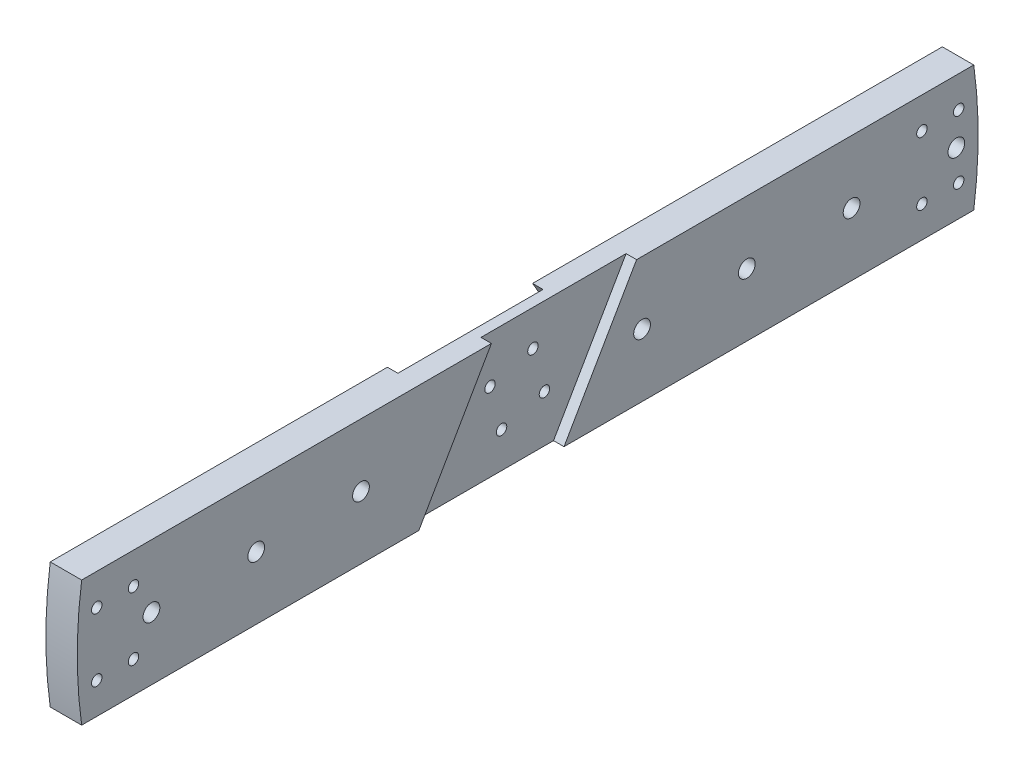
SolidWorks part; units mm, degrees
note: The reader was unsure of these and kept them because the rebuilt part matched: shared geometry of "Sketch3<5>".
ref_plane "Front Plane" through (0, 0, 0) normal (0, 0, 1) x (1, 0, 0)
ref_plane "Top Plane" through (0, 0, 0) normal (0, 1, 0) x (1, 0, 0)
ref_plane "Right Plane" through (0, 0, 0) normal (1, 0, 0) x (0, 0, -1)
sketch "Sketch1" plane through (0, 0, 0) normal (1, 0, 0) x (0, 0, -1)
  circle A0 centre (0, 0) radius 273.05
  point P0 (0, 0)
  dimension "D1" = 546.1
curve "Helix/Spiral1"
sketch "Sketch2" plane through (0, 0, 0) normal (1, 0, 0) x (0, 0, -1)
  line L0 (-273.05, 0) -> (273.05, 0) construction
  line L1 (-270.3788, -38.1) -> (270.3788, -38.1)
  line L3 (-270.3788, 38.1) -> (270.3788, 38.1)
  line L4 (270.3788, -38.1) -> (270.3788, 38.1) construction
  line L5 (-270.3788, -38.1) -> (270.3788, 38.1) construction
  line L6 (-270.3788, 38.1) -> (270.3788, -38.1) construction
  line L7 (273.05, 0) -> (228.6, 0) construction
  line L8 (38.1, -38.1) -> (-38.1, -38.1)
  line L9 (38.1, -38.1) -> (38.1, 38.1)
  line L10 (38.1, 38.1) -> (-38.1, 38.1)
  line L11 (-38.1, -38.1) -> (-38.1, 38.1)
  line L12 (38.1, -38.1) -> (-38.1, 38.1) construction
  line L13 (38.1, 38.1) -> (-38.1, -38.1) construction
  line L14 (226.3636, 31.8977) -> (270.3788, 38.1)
  line L15 (16.4978, -9.525) -> (-9.525, -16.4978)
  line L16 (273.05, 0) -> (250.825, 0)
  line L17 (250.825, 0) -> (228.6, 0)
  line L18 (16.4978, -9.525) -> (9.525, 16.4978)
  line L19 (-9.525, -16.4978) -> (-16.4978, 9.525)
  line L20 (0, 38.1) -> (0, -38.1) construction
  line L21 (9.525, 16.4978) -> (-16.4978, 9.525)
  line L26 (0, 0) -> (21.997, 38.1)
  circle A0 centre (0, 0) radius 273.05 construction
  circle A3 centre (196.3202, 0) radius 5.08
  circle A4 centre (132.8204, 0) radius 5.08
  circle A6 centre (-101.0705, 0) radius 5.08
  circle A7 centre (-164.5703, 0) radius 5.08
  circle A8 centre (-228.0701, 0) radius 5.08
  circle A9 centre (0, 0) radius 273.05
  circle A10 centre (0, 0) radius 228.6
  arc A11 (247.9144, -38.1) -> (250.825, 0) centre (0, 0) ccw
  arc A12 (236.6653, -38.1) -> (239.7125, 0) centre (0, 0) ccw
  arc A13 (259.1518, -38.1) -> (261.9375, 0) centre (0, 0) ccw
  circle A14 centre (238.9495, -19.1108) radius 3.175
  circle A15 centre (261.2401, -19.1009) radius 3.175
  circle A16 centre (238.9495, 19.1108) radius 3.175
  circle A17 centre (261.2401, 19.1009) radius 3.175
  circle A34 centre (-16.4978, 9.525) radius 3.175
  circle A35 centre (9.525, 16.4978) radius 3.175
  circle A36 centre (-9.525, -16.4978) radius 3.175
  circle A37 centre (16.4978, -9.525) radius 3.175
  circle A38 centre (-261.2401, -19.1009) radius 3.175
  circle A39 centre (-238.9495, -19.1108) radius 3.175
  circle A40 centre (-238.9495, 19.1108) radius 3.175
  circle A41 centre (-261.2401, 19.1009) radius 3.175
  circle A42 centre (259.8208, 0) radius 5.08
  circle A43 centre (69.3206, 0) radius 5.08
  spline S0 degree 3 poles (793.7729, 2436.9325) (-868.0473, 115.5273) (-235.8062, -393.7047) (104.0483, -251.1749) (112.0797, -247.3314) (127.6988, -238.8914) (135.2864, -234.2949) (149.9478, -224.399) (157.0216, -219.0994) (170.591, -207.8536) (177.0865, -201.9073) (189.4408, -189.4299) (195.2996, -182.8989) (206.3286, -169.3195) (211.4988, -162.2712) (221.1058, -147.7289) (225.5427, -140.2351) (233.6456, -124.8774) (237.3117, -117.0137) (243.8435, -100.9949) (246.7093, -92.8399) (251.6186, -76.3196) (253.6623, -67.9542) (256.914, -51.0955) (258.1221, -42.6021) (259.6972, -25.5701) (260.0643, -17.0316) (259.9603, 0.0078) (259.4892, 8.5087) (257.7198, 25.391) (256.4215, 33.7725) (253.0164, 50.336) (250.9097, 58.5181) (245.9143, 74.6055) (243.0257, 82.5107) (236.5004, 97.9701) (232.8637, 105.5243) (220.8931, 127.5551) (211.4954, 141.3972) (190.2687, 166.8872) (178.4403, 178.5347) (152.8439, 199.2225) (139.0766, 208.2626) (110.1609, 223.4294) (95.0134, 229.556) (63.9404, 238.7068) (48.0158, 241.7309) (16.0122, 244.61) (-0.066, 244.4649) (-31.7571, 241.062) (-47.3693, 237.8044) (-77.5368, 228.3514) (-92.0913, 222.1565) (-119.6019, 207.1148) (-132.5574, 198.2684) (-156.3988, 178.3067) (-167.2843, 167.192) (-186.602, 143.1579) (-195.0339, 130.2393) (-209.1618, 103.1232) (-214.8575, 88.9267) (-223.3403, 59.8215) (-226.1274, 44.9136) (-228.7351, 14.9702) (-228.556, -0.0645) (-225.289, -29.6821) (-222.2014, -44.2642) (-213.2863, -72.4244) (-207.4591, -86.0018) (-193.3365, -111.6487) (-185.0414, -123.7176) (-166.3447, -145.9104) (-155.9437, -156.0339) (-133.472, -173.9815) (-121.4019, -181.8053) (-96.0856, -194.8941) (-82.8399, -200.159) (-55.7025, -207.9738) (-41.8113, -210.5238) (-13.9282, -212.8603) (0.063, -212.647) (27.607, -209.5159) (41.159, -206.5984) (67.312, -198.2211) (79.9123, -192.7617) (103.6955, -179.5582) (114.8778, -171.8144) (135.422, -154.3828) (144.7835, -144.6954) (161.361, -123.7861) (168.5766, -112.5646) (180.6265, -89.0479) (185.4604, -76.7532) (192.6073, -51.5835) (194.9202, -38.7091) (196.9855, -12.8863) (196.738, 0.0615) (193.7429, 25.5319) (190.9954, 38.0539) (183.156, 62.1997) (178.0643, 73.8229) (165.7798, 95.7423) (158.5874, 106.038) (142.4208, 124.9336) (133.4471, 133.5331) (114.1001, 148.7404) (103.7273, 155.348) (82.0102, 166.3588) (70.6665, 170.7619) (47.4645, 177.2408) (35.6069, 179.3167) (11.8443, 181.1107) (-0.0601, 180.8291) (-23.4569, 177.9698) (-34.9488, 175.3924) (-57.0873, 168.0908) (-67.7334, 163.3669) (-87.7891, 152.0015) (-97.1983, 145.3604) (-114.4453, 130.4588) (-122.2827, 122.1989) (-136.1199, 104.4142) (-142.1193, 94.89) (-152.0911, 74.9725) (-156.0634, 64.5798) (-161.8743, 43.3455) (-163.7131, 32.5046) (-165.2359, 10.8023) (-164.9201, -0.0586) (-162.1968, -21.3818) (-159.7894, -31.8436) (-153.0257, -51.9749) (-148.6695, -61.6439) (-138.2232, -79.8359) (-132.1334, -88.3585) (-118.4968, -103.9569) (-110.9506, -111.0324) (-94.7282, -123.4994) (-86.0527, -128.8907) (-67.9348, -137.8235) (-58.493, -141.3648) (-39.2266, -146.5079) (-29.4024, -148.1095) (-9.7603, -149.3611) (0.0571, -149.0111) (19.3067, -146.4237) (28.7385, -144.1864) (46.8626, -137.9605) (55.5545, -133.9721) (71.8827, -124.4449) (79.5187, -118.9064) (93.4685, -106.5349) (99.782, -99.7023) (110.8788, -85.0423) (115.6621, -77.2154) (123.5558, -60.8971) (126.6663, -52.4063) (131.1414, -35.1076) (132.506, -26.3002) (133.4863, -8.7184) (133.1022, 0.0556) (130.6506, 17.2317) (128.5834, 25.6333) (122.8954, 41.7502) (119.2747, 49.465) (110.6666, 63.9295) (105.6794, 70.6789) (94.5729, 82.9801) (88.454, 88.5316) (75.3564, 98.2583) (68.3781, 102.4334) (53.8594, 109.2882) (46.3196, 111.9678) (30.9886, 115.7749) (23.198, 116.9024) (7.6764, 117.6115) (-0.0541, 117.1932) (-15.1566, 114.8776) (-22.5282, 112.9804) (-36.6378, 107.8302) (-43.3755, 104.5773) (-55.9763, 96.8883) (-61.8391, 92.4524) (-72.4917, 82.6109) (-77.2812, 77.2057) (-85.6378, 65.6704) (-89.2048, 59.5407) (-95.0205, 46.8218) (-97.2692, 40.2329) (-100.4084, 26.8696) (-101.2988, 20.0957) (-101.7367, 6.6344) (-101.2842, -0.0526) (-99.1045, -13.0815) (-97.3775, -19.4231) (-92.765, -31.5255) (-89.8799, -37.2861) (-83.11, -48.0231) (-79.2254, -52.9994) (-70.649, -62.0033) (-65.9574, -66.0308) (-55.9845, -73.0173) (-50.7034, -75.9761) (-39.7841, -80.7528) (-34.1461, -82.5707) (-22.7507, -85.0419) (-16.9935, -85.6952) (-5.5924, -85.8619) (0.0512, -85.3753) (11.0065, -83.3315) (16.3179, -81.7745) (26.4131, -77.6999) (31.1966, -75.1825) (40.0699, -69.3317) (44.1596, -65.9984) (51.5149, -58.687) (54.7804, -54.7091) (60.3967, -46.2985) (62.7475, -41.8661) (66.4852, -32.7464) (67.8722, -28.0594) (69.6754, -18.6317) (70.0917, -13.8913) (69.9871, -4.5505) (69.4663, 0.0497) (67.5584, 8.9314) (66.1715, 13.2128) (62.6347, 21.3007) (60.4851, 25.1071) (55.5534, 32.1167) (52.7714, 35.3198) (46.725, 41.0265) (43.4608, 43.53) (36.6126, 47.7762) (33.0288, 49.5188) (25.7087, 52.2175) (21.9727, 53.1736) (14.5127, 54.3089) (10.789, 54.4881) (3.5085, 54.1123) (-0.0482, 53.5574) (-6.8563, 51.7854) (-10.1076, 50.5685) (-16.1884, 47.5696) (-19.0177, 45.7877) (-24.1635, 41.7751) (-26.48, 39.5444) (-30.5381, 34.763) (-32.2797, 32.2125) (-35.1557, 26.9267) (-36.2902, 24.1915) (-37.9498, 18.671) (-38.4751, 15.8859) (-38.9424, 10.3937) (-38.8845, 7.6868) (-38.2375, 2.4665) (-37.6484, -0.0467) (-36.0123, -4.7813) (-34.9655, -7.0025) (-32.5044, -11.076) (-31.0903, -12.9282) (-27.9967, -16.2103) (-26.3174, -17.6402) (-22.8011, -20.0497) (-20.9643, -21.0293) (-17.2407, -22.5352) (-15.3542, -23.0615) (-11.6333, -23.6822) (-9.7992, -23.7765) (-6.2748, -23.5759) (-4.5846, -23.281) (-1.4245, -22.3627) (0.0452, -21.7394) (56.9085, 10.3181) (-130.2763, 262.2935) (-1920.1654, -2304.1586) knots -0.153771 -0.153771 -0.153771 -0.153771 0.003906 0.003906 0.007813 0.007813 0.011719 0.011719 0.015625 0.015625 0.019531 0.019531 0.023438 0.023438 0.027344 0.027344 0.03125 0.03125 0.035156 0.035156 0.039063 0.039063 0.042969 0.042969 0.046875 0.046875 0.050781 0.050781 0.054688 0.054688 0.058594 0.058594 0.0625 0.0625 0.066406 0.066406 0.070313 0.070313 0.078125 0.078125 0.085938 0.085938 0.09375 0.09375 0.101562 0.101562 0.109375 0.109375 0.117187 0.117187 0.125 0.125 0.132812 0.132812 0.140625 0.140625 0.148437 0.148437 0.15625 0.15625 0.164062 0.164062 0.171875 0.171875 0.179687 0.179687 0.1875 0.1875 0.195312 0.195312 0.203125 0.203125 0.210937 0.210937 0.21875 0.21875 0.226562 0.226562 0.234375 0.234375 0.242187 0.242187 0.25 0.25 0.257812 0.257812 0.265625 0.265625 0.273437 0.273437 0.28125 0.28125 0.289062 0.289062 0.296875 0.296875 0.304687 0.304687 0.3125 0.3125 0.320312 0.320312 0.328125 0.328125 0.335937 0.335937 0.34375 0.34375 0.351562 0.351562 0.359375 0.359375 0.367187 0.367187 0.375 0.375 0.382812 0.382812 0.390625 0.390625 0.398437 0.398437 0.40625 0.40625 0.414062 0.414062 0.421875 0.421875 0.429687 0.429687 0.4375 0.4375 0.445312 0.445312 0.453125 0.453125 0.460937 0.460937 0.46875 0.46875 0.476562 0.476562 0.484375 0.484375 0.492187 0.492187 0.5 0.5 0.507812 0.507812 0.515625 0.515625 0.523437 0.523437 0.53125 0.53125 0.539062 0.539062 0.546875 0.546875 0.554687 0.554687 0.5625 0.5625 0.570312 0.570312 0.578125 0.578125 0.585937 0.585937 0.59375 0.59375 0.601562 0.601562 0.609375 0.609375 0.617187 0.617187 0.625 0.625 0.632812 0.632812 0.640625 0.640625 0.648438 0.648438 0.65625 0.65625 0.664062 0.664062 0.671875 0.671875 0.679688 0.679688 0.6875 0.6875 0.695312 0.695312 0.703125 0.703125 0.710938 0.710938 0.71875 0.71875 0.726562 0.726562 0.734375 0.734375 0.742188 0.742188 0.75 0.75 0.757812 0.757812 0.765625 0.765625 0.773438 0.773438 0.78125 0.78125 0.789062 0.789062 0.796875 0.796875 0.804688 0.804688 0.8125 0.8125 0.820312 0.820312 0.828125 0.828125 0.835938 0.835938 0.84375 0.84375 0.851562 0.851562 0.859375 0.859375 0.867188 0.867188 0.875 0.875 0.882813 0.882813 0.890625 0.890625 0.898438 0.898438 0.90625 0.90625 0.914063 0.914063 0.921875 0.921875 0.929688 0.929688 0.9375 0.9375 0.945313 0.945313 0.953125 0.953125 0.960938 0.960938 0.96875 0.96875 0.976563 0.976563 0.984375 0.984375 0.992188 0.992188 1.318271 1.318271 1.318271 1.318271 only from (70.6705, -263.746) to (4.9305, -18.4009) construction
  spline S1 degree 3 poles (70.6705, -263.746) (79.216, -261.1139) (87.6164, -258.0662) (104.0483, -251.1749) (112.0797, -247.3314) (127.6988, -238.8914) (135.2864, -234.2949) (149.9478, -224.399) (157.0216, -219.0994) (170.591, -207.8536) (177.0865, -201.9073) (189.4408, -189.4299) (195.2996, -182.8989) (206.3286, -169.3195) (211.4988, -162.2712) (221.1058, -147.7289) (225.5427, -140.2351) (233.6456, -124.8774) (237.3117, -117.0137) (243.8435, -100.9949) (246.7093, -92.8399) (251.6186, -76.3196) (253.6623, -67.9542) (256.914, -51.0955) (258.1221, -42.6021) (259.6972, -25.5701) (260.0643, -17.0316) (259.9603, 0.0078) (259.4892, 8.5087) (257.7198, 25.391) (256.4215, 33.7725) (253.0164, 50.336) (250.9097, 58.5181) (245.9143, 74.6055) (243.0257, 82.5107) (236.5004, 97.9701) (232.8637, 105.5243) (220.8931, 127.5551) (211.4954, 141.3972) (190.2687, 166.8872) (178.4403, 178.5347) (152.8439, 199.2225) (139.0766, 208.2626) (110.1609, 223.4294) (95.0134, 229.556) (63.9404, 238.7068) (48.0158, 241.7309) (16.0122, 244.61) (-0.066, 244.4649) (-31.7571, 241.062) (-47.3693, 237.8044) (-77.5368, 228.3514) (-92.0913, 222.1565) (-119.6019, 207.1148) (-132.5574, 198.2684) (-156.3988, 178.3067) (-167.2843, 167.192) (-186.602, 143.1579) (-195.0339, 130.2393) (-209.1618, 103.1232) (-214.8575, 88.9267) (-223.3403, 59.8215) (-226.1274, 44.9136) (-228.7351, 14.9702) (-228.556, -0.0645) (-225.289, -29.6821) (-222.2014, -44.2642) (-213.2863, -72.4244) (-207.4591, -86.0018) (-193.3365, -111.6487) (-185.0414, -123.7176) (-166.3447, -145.9104) (-155.9437, -156.0339) (-133.472, -173.9815) (-121.4019, -181.8053) (-96.0856, -194.8941) (-82.8399, -200.159) (-55.7025, -207.9738) (-41.8113, -210.5238) (-13.9282, -212.8603) (0.063, -212.647) (27.607, -209.5159) (41.159, -206.5984) (67.312, -198.2211) (79.9123, -192.7617) (103.6955, -179.5582) (114.8778, -171.8144) (135.422, -154.3828) (144.7835, -144.6954) (161.361, -123.7861) (168.5766, -112.5646) (180.6265, -89.0479) (185.4604, -76.7532) (192.6073, -51.5835) (194.9202, -38.7091) (196.9855, -12.8863) (196.738, 0.0615) (193.7429, 25.5319) (190.9954, 38.0539) (183.156, 62.1997) (178.0643, 73.8229) (165.7798, 95.7423) (158.5874, 106.038) (142.4208, 124.9336) (133.4471, 133.5331) (114.1001, 148.7404) (103.7273, 155.348) (82.0102, 166.3588) (70.6665, 170.7619) (47.4645, 177.2408) (35.6069, 179.3167) (11.8443, 181.1107) (-0.0601, 180.8291) (-23.4569, 177.9698) (-34.9488, 175.3924) (-57.0873, 168.0908) (-67.7334, 163.3669) (-87.7891, 152.0015) (-97.1983, 145.3604) (-114.4453, 130.4588) (-122.2827, 122.1989) (-136.1199, 104.4142) (-142.1193, 94.89) (-152.0911, 74.9725) (-156.0634, 64.5798) (-161.8743, 43.3455) (-163.7131, 32.5046) (-165.2359, 10.8023) (-164.9201, -0.0586) (-162.1968, -21.3818) (-159.7894, -31.8436) (-153.0257, -51.9749) (-148.6695, -61.6439) (-138.2232, -79.8359) (-132.1334, -88.3585) (-118.4968, -103.9569) (-110.9506, -111.0324) (-94.7282, -123.4994) (-86.0527, -128.8907) (-67.9348, -137.8235) (-58.493, -141.3648) (-39.2266, -146.5079) (-29.4024, -148.1095) (-9.7603, -149.3611) (0.0571, -149.0111) (19.3067, -146.4237) (28.7385, -144.1864) (46.8626, -137.9605) (55.5545, -133.9721) (71.8827, -124.4449) (79.5187, -118.9064) (93.4685, -106.5349) (99.782, -99.7023) (110.8788, -85.0423) (115.6621, -77.2154) (123.5558, -60.8971) (126.6663, -52.4063) (131.1414, -35.1076) (132.506, -26.3002) (133.4863, -8.7184) (133.1022, 0.0556) (130.6506, 17.2317) (128.5834, 25.6333) (122.8954, 41.7502) (119.2747, 49.465) (110.6666, 63.9295) (105.6794, 70.6789) (94.5729, 82.9801) (88.454, 88.5316) (75.3564, 98.2583) (68.3781, 102.4334) (53.8594, 109.2882) (46.3196, 111.9678) (30.9886, 115.7749) (23.198, 116.9024) (7.6764, 117.6115) (-0.0541, 117.1932) (-15.1566, 114.8776) (-22.5282, 112.9804) (-36.6378, 107.8302) (-43.3755, 104.5773) (-55.9763, 96.8883) (-61.8391, 92.4524) (-72.4917, 82.6109) (-77.2812, 77.2057) (-85.6378, 65.6704) (-89.2048, 59.5407) (-95.0205, 46.8218) (-97.2692, 40.2329) (-100.4084, 26.8696) (-101.2988, 20.0957) (-101.7367, 6.6344) (-101.2842, -0.0526) (-99.1045, -13.0815) (-97.3775, -19.4231) (-92.765, -31.5255) (-89.8799, -37.2861) (-83.11, -48.0231) (-79.2254, -52.9994) (-70.649, -62.0033) (-65.9574, -66.0308) (-55.9845, -73.0173) (-50.7034, -75.9761) (-39.7841, -80.7528) (-34.1461, -82.5707) (-22.7507, -85.0419) (-16.9935, -85.6952) (-5.5924, -85.8619) (0.0512, -85.3753) (11.0065, -83.3315) (16.3179, -81.7745) (26.4131, -77.6999) (31.1966, -75.1825) (40.0699, -69.3317) (44.1596, -65.9984) (51.5149, -58.687) (54.7804, -54.7091) (60.3967, -46.2985) (62.7475, -41.8661) (66.4852, -32.7464) (67.8722, -28.0594) (69.6754, -18.6317) (70.0917, -13.8913) (69.9871, -4.5505) (69.4663, 0.0497) (67.5584, 8.9314) (66.1715, 13.2128) (62.6347, 21.3007) (60.4851, 25.1071) (55.5534, 32.1167) (52.7714, 35.3198) (46.725, 41.0265) (43.4608, 43.53) (36.6126, 47.7762) (33.0288, 49.5188) (25.7087, 52.2175) (21.9727, 53.1736) (14.5127, 54.3089) (10.789, 54.4881) (3.5085, 54.1123) (-0.0482, 53.5574) (-6.8563, 51.7854) (-10.1076, 50.5685) (-16.1884, 47.5696) (-19.0177, 45.7877) (-24.1635, 41.7751) (-26.48, 39.5444) (-30.5381, 34.763) (-32.2797, 32.2125) (-35.1557, 26.9267) (-36.2902, 24.1915) (-37.9498, 18.671) (-38.4751, 15.8859) (-38.9424, 10.3937) (-38.8845, 7.6868) (-38.2375, 2.4665) (-37.6484, -0.0467) (-36.0123, -4.7813) (-34.9655, -7.0025) (-32.5044, -11.076) (-31.0903, -12.9282) (-27.9967, -16.2103) (-26.3174, -17.6402) (-22.8011, -20.0497) (-20.9643, -21.0293) (-17.2407, -22.5352) (-15.3542, -23.0615) (-11.6333, -23.6822) (-9.7992, -23.7765) (-6.2748, -23.5759) (-4.5846, -23.281) (-1.4245, -22.3627) (0.0452, -21.7394) (2.7062, -20.2393) (3.8974, -19.3625) (4.9305, -18.4009) knots 0 0 0 0 0.003906 0.003906 0.007813 0.007813 0.011719 0.011719 0.015625 0.015625 0.019531 0.019531 0.023438 0.023438 0.027344 0.027344 0.03125 0.03125 0.035156 0.035156 0.039063 0.039063 0.042969 0.042969 0.046875 0.046875 0.050781 0.050781 0.054688 0.054688 0.058594 0.058594 0.0625 0.0625 0.066406 0.066406 0.070313 0.070313 0.078125 0.078125 0.085938 0.085938 0.09375 0.09375 0.101562 0.101562 0.109375 0.109375 0.117187 0.117187 0.125 0.125 0.132812 0.132812 0.140625 0.140625 0.148437 0.148437 0.15625 0.15625 0.164062 0.164062 0.171875 0.171875 0.179687 0.179687 0.1875 0.1875 0.195312 0.195312 0.203125 0.203125 0.210937 0.210937 0.21875 0.21875 0.226562 0.226562 0.234375 0.234375 0.242187 0.242187 0.25 0.25 0.257812 0.257812 0.265625 0.265625 0.273437 0.273437 0.28125 0.28125 0.289062 0.289062 0.296875 0.296875 0.304687 0.304687 0.3125 0.3125 0.320312 0.320312 0.328125 0.328125 0.335937 0.335937 0.34375 0.34375 0.351562 0.351562 0.359375 0.359375 0.367187 0.367187 0.375 0.375 0.382812 0.382812 0.390625 0.390625 0.398437 0.398437 0.40625 0.40625 0.414062 0.414062 0.421875 0.421875 0.429687 0.429687 0.4375 0.4375 0.445312 0.445312 0.453125 0.453125 0.460937 0.460937 0.46875 0.46875 0.476562 0.476562 0.484375 0.484375 0.492187 0.492187 0.5 0.5 0.507812 0.507812 0.515625 0.515625 0.523437 0.523437 0.53125 0.53125 0.539062 0.539062 0.546875 0.546875 0.554687 0.554687 0.5625 0.5625 0.570312 0.570312 0.578125 0.578125 0.585937 0.585937 0.59375 0.59375 0.601562 0.601562 0.609375 0.609375 0.617187 0.617187 0.625 0.625 0.632812 0.632812 0.640625 0.640625 0.648438 0.648438 0.65625 0.65625 0.664062 0.664062 0.671875 0.671875 0.679688 0.679688 0.6875 0.6875 0.695312 0.695312 0.703125 0.703125 0.710938 0.710938 0.71875 0.71875 0.726562 0.726562 0.734375 0.734375 0.742188 0.742188 0.75 0.75 0.757812 0.757812 0.765625 0.765625 0.773438 0.773438 0.78125 0.78125 0.789062 0.789062 0.796875 0.796875 0.804688 0.804688 0.8125 0.8125 0.820312 0.820312 0.828125 0.828125 0.835938 0.835938 0.84375 0.84375 0.851562 0.851562 0.859375 0.859375 0.867188 0.867188 0.875 0.875 0.882813 0.882813 0.890625 0.890625 0.898438 0.898438 0.90625 0.90625 0.914063 0.914063 0.921875 0.921875 0.929688 0.929688 0.9375 0.9375 0.945313 0.945313 0.953125 0.953125 0.960938 0.960938 0.96875 0.96875 0.976563 0.976563 0.984375 0.984375 0.992188 0.992188 1 1 1 1 construction
  point P0 (0, 0)
  point P26 (0, 0)
  point P37 (250.825, 0)
  point P40 (239.7125, 0)
  point P45 (261.9375, 0)
  point P46 (238.9495, -19.1108)
  point P64 (261.2401, -19.1009)
  dimension "D2" = 10.16
  dimension "D4" = 457.2
  dimension "D5" = 6.35
  dimension "D1" = 76.2
  dimension "D3" = 76.2
  dimension "D6" = 30
extrude "Boss-Extrude1" add sketch "Sketch2" along normal blind 19.05
sketch "Sketch3" plane through (19.05, 0, 0) normal (1, 0, 0) x (0, 0, -1)
  line L0 (-270.3788, 38.1) -> (270.3788, 38.1) construction
  line L1 (38.1, -38.1) -> (-38.1, -38.1)
  line L2 (38.1, -38.1) -> (38.1, 38.1)
  line L3 (38.1, 38.1) -> (-38.1, 38.1)
  line L4 (-38.1, -38.1) -> (-38.1, 38.1)
  line L5 (38.1, -38.1) -> (-38.1, 38.1) construction
  line L6 (38.1, 38.1) -> (-38.1, -38.1) construction
  line L7 (-65.9911, -38.1) -> (21.997, -38.1)
  line L8 (-65.9911, -38.1) -> (-21.997, 38.1)
  line L9 (21.997, -38.1) -> (65.9911, 38.1)
  line L10 (-21.997, 38.1) -> (65.9911, 38.1)
  line L11 (-270.3788, -38.1) -> (270.3788, -38.1) construction
  line L12 (-21.997, 38.1) -> (21.997, -38.1) construction
  line L13 (0, 300.355) -> (0, -300.355) construction
  line L14 (-21.997, -38.1) -> (-65.9911, 38.1)
  line L15 (21.997, 38.1) -> (-65.9911, 38.1)
  line L16 (65.9911, -38.1) -> (21.997, 38.1)
  line L17 (65.9911, -38.1) -> (-21.997, -38.1)
  point P0 (0, 0)
  point P14 (0, 0)
  dimension "D1" = 76.2
  dimension "D2" = 76.2
  dimension "D3" = 60
extrude "Cut-Extrude2" cut sketch "Sketch3" against normal blind 6.35 from offset 12.7 offset against normal yes
extrude "Cut-Extrude3" cut sketch "Sketch3<5>" against normal blind 6.35
sketch "Sketch3<5>" plane through (19.05, 0, 0) normal (1, 0, 0) x (0, 0, -1) same geometry as "Sketch3"
